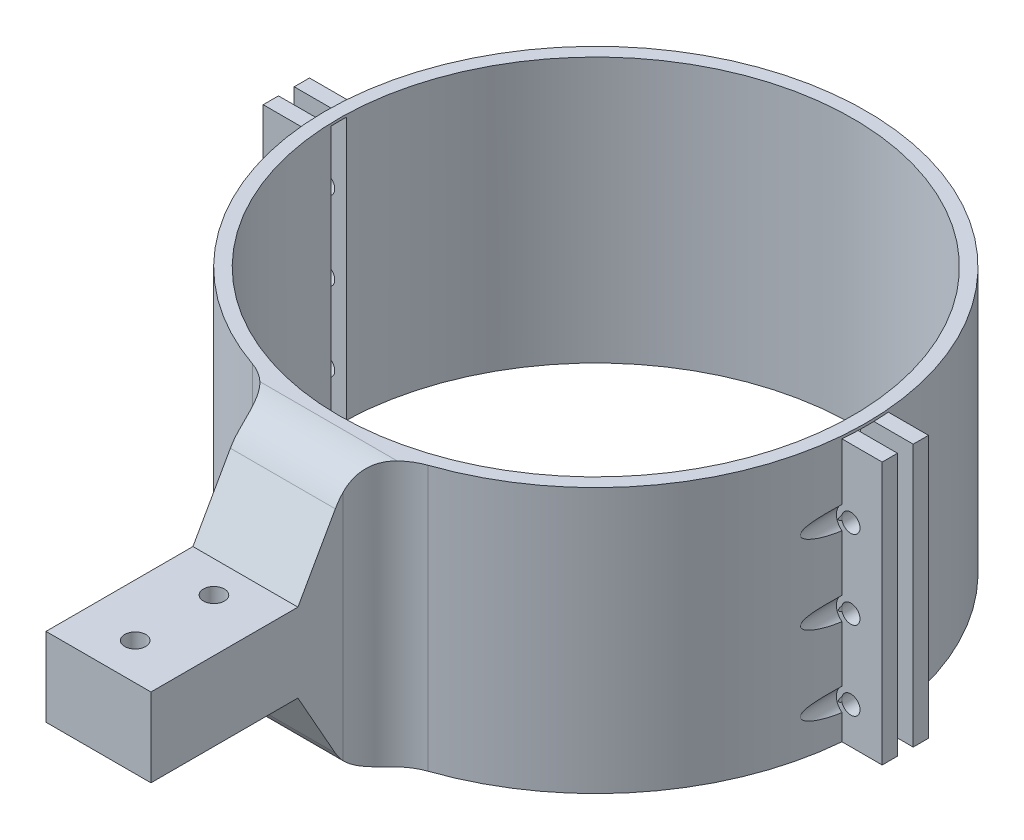
SolidWorks part; units mm, degrees
ref_plane "Front Plane" through (0, 0, 0) normal (0, 0, 1) x (1, 0, 0)
ref_plane "Top Plane" through (0, 0, 0) normal (0, 1, 0) x (1, 0, 0)
ref_plane "Right Plane" through (0, 0, 0) normal (1, 0, 0) x (0, 0, -1)
sketch "Sketch1" plane through (0, 0, 0) normal (0, 1, 0) x (1, 0, 0)
  line L0 (-68.1891, 0) -> (51.75, 0) construction
  line L1 (-58.977, -1.5) -> (-48.977, -1.5)
  line L2 (-58.977, 1.5) -> (-48.977, 1.5)
  line L3 (-58.977, -1.5) -> (-58.977, -4.4106)
  line L4 (-58.977, -4.4106) -> (-51.3108, -4.4106)
  line L5 (-58.977, 1.5) -> (-58.977, 4.4106)
  line L6 (-58.977, 4.4106) -> (-51.3108, 4.4106)
  line L7 (0, -59.7416) -> (0, 60.0429) construction
  line L8 (58.977, -1.5) -> (48.977, -1.5)
  line L9 (58.977, -4.4106) -> (51.3108, -4.4106)
  line L10 (58.977, -1.5) -> (58.977, -4.4106)
  line L11 (58.977, 1.5) -> (48.977, 1.5)
  line L12 (58.977, 1.5) -> (58.977, 4.4106)
  line L13 (58.977, 4.4106) -> (51.3108, 4.4106)
  arc A0 (-48.977, -1.5) -> (48.977, -1.5) centre (0, 0) ccw
  arc A1 (-51.5, 0) -> (-51.4782, -1.5) centre (0, 0) ccw
  circle A2 centre (0, 0) radius 51.5 construction
  circle A3 centre (0, 0) radius 49 construction
  arc A4 (-51.3108, -4.4106) -> (51.3108, -4.4106) centre (0, 0) ccw
  arc A5 (48.977, 1.5) -> (-48.977, 1.5) centre (0, 0) ccw
  arc A6 (51.3108, 4.4106) -> (-51.3108, 4.4106) centre (0, 0) ccw
  dimension "D1" = 98
  dimension "D3" = 3
  dimension "D4" = 10
  dimension "D2" = 2.5
extrude "Boss-Extrude1" add sketch "Sketch1" along normal blind 50 contours L4 A4 L9 L10 L8 A0 L1 L3 | A6 L6 L5 L2 A5 L11 L12 L13 region at (-55.2276, 0, 2.7811)
sketch "Sketch2" plane through (0, 0, 4.4106) normal (0, 0, 1) x (1, 0, 0)
  line L0 (0, 57.4382) -> (0, -5.5464) construction
  line L1 (-53, 59.7194) -> (-53, -8.2171) construction
  line L2 (-58.977, 0) -> (-51.3108, 0) construction
  circle A0 centre (-53, 7) radius 1.75
  circle A1 centre (-53, 22) radius 1.75
  circle A2 centre (-53, 37) radius 1.75
  circle A3 centre (53, 7) radius 1.75
  circle A4 centre (53, 22) radius 1.75
  circle A5 centre (53, 37) radius 1.75
  dimension "D5" = 3.5
  dimension "D6" = 3.5
  dimension "D7" = 3.5
  dimension "D1" = 53
  dimension "D2" = 7
  dimension "D3" = 15
  dimension "D4" = 15
extrude "Cut-Extrude1" cut sketch "Sketch2" against normal through all
sketch "Sketch3" plane through (0, 0, 4.4106) normal (0, 0, 1) x (1, 0, 0)
  line L0 (0, 54.5816) -> (0, -6.8451) construction
  circle A0 centre (-53, 37) radius 2.75
  circle A1 centre (-53, 22) radius 2.75
  circle A2 centre (-53, 7) radius 2.75
  circle A3 centre (53, 7) radius 2.75
  circle A4 centre (53, 22) radius 2.75
  circle A5 centre (53, 37) radius 2.75
  circle A6 centre (53, 7) radius 1.75 construction
  circle A7 centre (53, 22) radius 1.75 construction
  circle A8 centre (53, 37) radius 1.75 construction
  circle A9 centre (-53, 7) radius 1.75 construction
  circle A10 centre (-53, 22) radius 1.75 construction
  circle A11 centre (-53, 37) radius 1.75 construction
  circle A12 centre (53, 7) radius 1.75
  circle A13 centre (53, 22) radius 1.75
  circle A14 centre (53, 37) radius 1.75
  circle A15 centre (-53, 7) radius 1.75
  circle A16 centre (-53, 22) radius 1.75
  circle A17 centre (-53, 37) radius 1.75
  dimension "D2" = 5.5
  dimension "D3" = 5.5
  dimension "D4" = 5.5
extrude "Cut-Extrude3" cut sketch "Sketch3" along normal blind 50
ref_plane "Plane1" through (0, 0, 0) normal (0, 0, 1) x (0, -1, 0)
sketch "Sketch5" plane through (0, 0, -4.4106) normal (0, 0, -1) x (-1, 0, 0)
  line L0 (0, 54.4273) -> (0, -7.504) construction
  line L1 (0, 50) -> (0, 0) construction
  circle A0 centre (53, 7) radius 1.75 construction
  circle A1 centre (53, 22) radius 1.75 construction
  circle A2 centre (53, 37) radius 1.75 construction
  circle A3 centre (-53, 7) radius 1.75 construction
  circle A4 centre (-53, 22) radius 1.75 construction
  circle A5 centre (-53, 37) radius 1.75 construction
  circle A6 centre (53, 7) radius 1.75
  circle A7 centre (53, 22) radius 1.75
  circle A8 centre (53, 37) radius 1.75
  circle A9 centre (-53, 7) radius 1.75
  circle A10 centre (-53, 22) radius 1.75
  circle A11 centre (-53, 37) radius 1.75
  circle A12 centre (-53, 37) radius 2.75
  circle A13 centre (-53, 22) radius 2.75
  circle A14 centre (-53, 7) radius 2.75
  circle A15 centre (53, 7) radius 2.75
  circle A16 centre (53, 22) radius 2.75
  circle A17 centre (53, 37) radius 2.75
  dimension "D1" = 5.5
  dimension "D2" = 5.5
  dimension "D3" = 5.5
extrude "Cut-Extrude4" cut sketch "Sketch5" along normal blind 50
sketch "Sketch11" plane through (0, 50, 0) normal (0, 1, 0) x (1, 0, 0)
  circle A2 centre (0, 0) radius 49
  circle A3 centre (0, 0) radius 51.5
extrude "Boss-Extrude2" add sketch "Sketch11" along normal blind 0.5
ref_plane "Plane2" through (0, 0, 0) normal (-1, 0, 0) x (0, -1, 0)
sketch "Sketch13" plane through (0, 0, 0) normal (-1, 0, 0) x (0, -1, 0)
  line L0 (-25.25, 51.5) -> (-25.25, 112.2597) construction
  line L1 (0, 51.5) -> (-50.5, 51.5) construction
  line L2 (-50.5, 50.0743) -> (0, 50.0743)
  line L3 (-50.5, 51.5) -> (-50.5, -51.5) construction
  line L4 (0, 4.4106) -> (0, 51.5) construction
  line L5 (0, 50.0743) -> (0, 56.7749)
  line L6 (0, 56.7749) -> (-17.75, 66.7749)
  line L7 (-17.75, 66.7749) -> (-17.75, 94.7749)
  line L8 (-17.75, 94.7749) -> (-32.75, 94.7749)
  line L9 (-32.75, 66.7749) -> (-32.75, 94.7749)
  line L10 (-50.5, 56.7749) -> (-32.75, 66.7749)
  line L11 (-50.5, 50.0743) -> (-50.5, 56.7749)
  point P16 (-25.25, 94.7749)
  dimension "D1" = 15
  dimension "D2" = 10
  dimension "D3" = 28
extrude "Boss-Extrude3" add sketch "Sketch13" along normal blind 10 and the other way blind 10
sketch "Sketch14" plane through (0, 32.75, 0) normal (0, 1, 0) x (1, 0, 0)
  line L0 (0, -66.7749) -> (0, -94.2967) construction
  line L1 (10, -66.7749) -> (-10, -66.7749) construction
  line L2 (10, -94.7749) -> (-10, -94.7749) construction
  circle A0 centre (0, -72.7749) radius 2
  circle A1 centre (0, -87.7749) radius 2
  point P9 (0, 0)
  point P10 (0, 0)
  dimension "D1" = 4
  dimension "D2" = 4
  dimension "D3" = 15
  dimension "D4" = 7
extrude "Cut-Extrude5" cut sketch "Sketch14" against normal through all
fillet "Fillet1" radius 10 2 edges at (-10, 25.25, 50.5198) (10, 25.25, 50.5198)
fillet "Fillet2" radius 10 2 edges at (0, 50.5, 56.7749) (0, 0, 56.7749)
